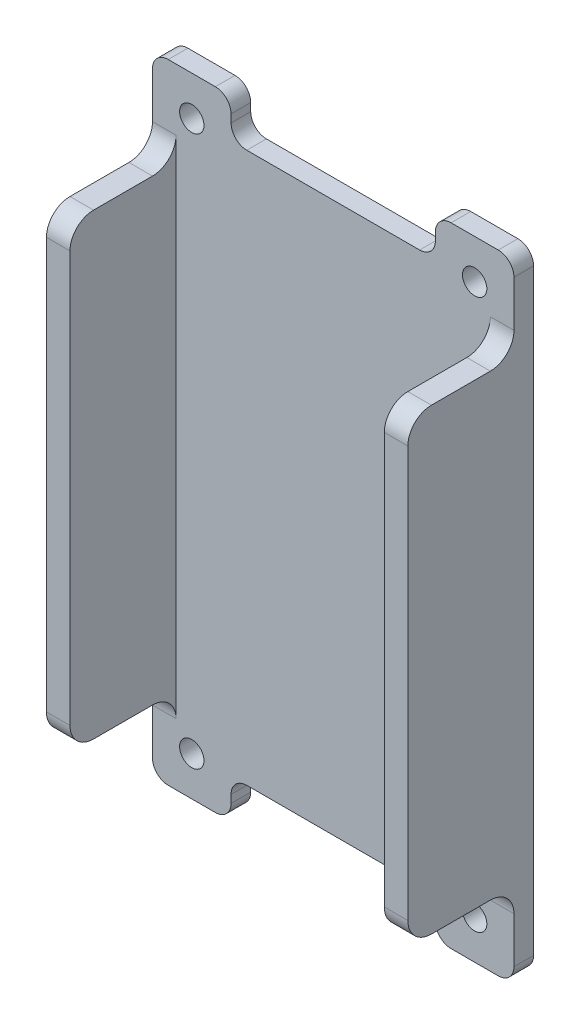
SolidWorks part; units mm, degrees
material "ABS"
ref_plane "Front Plane" through (0, 0, 0) normal (0, 0, 1) x (1, 0, 0)
ref_plane "Top Plane" through (0, 0, 0) normal (0, 1, 0) x (1, 0, 0)
ref_plane "Right Plane" through (0, 0, 0) normal (1, 0, 0) x (0, 0, -1)
sketch "Sketch1" plane through (0, 0, 0) normal (0, 0, 1) x (1, 0, 0)
  line L0 (0, -23.107) -> (0, 29972.0625) construction
  line L1 (-20, -19.15) -> (20, -19.15)
  line L2 (-20, -19.15) -> (-20, 39.15)
  line L3 (-20, 39.15) -> (20, 39.15)
  line L4 (20, -19.15) -> (20, 39.15)
  line L5 (-20, -19.15) -> (20, 39.15) construction
  line L6 (-20, 39.15) -> (20, -19.15) construction
  line L7 (4.4373, 10) -> (29962.6069, 10) construction
  line L8 (-13, 50) -> (-13, 45)
  line L10 (-23, -30) -> (-23, 50)
  line L11 (-23, 50) -> (-13, 50)
  line L12 (23, -30) -> (23, 50)
  line L13 (13, -30) -> (23, -30)
  line L14 (13, -25) -> (13, -30)
  line L15 (-13, 45) -> (13, 45)
  line L16 (13, 45) -> (13, 50)
  line L17 (13, 50) -> (23, 50)
  line L18 (-13, -25) -> (13, -25)
  line L19 (-13, -30) -> (-13, -25)
  line L20 (-23, -30) -> (-13, -30)
  line L21 (-23, 39.15) -> (-20, 39.15)
  line L22 (20, 39.15) -> (23, 39.15)
  line L23 (20, -19.15) -> (23, -19.15)
  line L24 (-20, -19.15) -> (-23, -19.15)
  circle A0 centre (-18, 45) radius 1.55
  circle A1 centre (18, 45) radius 1.55
  circle A2 centre (18, -25) radius 1.55
  circle A3 centre (-18, -25) radius 1.55
  point P0 (0, 10)
  point P10 (0, 10)
  point P26 (23, 10)
  point P33 (-23, 10)
  dimension "D3" = 3.1
  dimension "D1" = 40
  dimension "D2" = 58.3
  dimension "D4" = 3
  dimension "D5" = 5
  dimension "D6" = 5
  dimension "D7" = 5
  dimension "D8" = 5
  dimension "D9" = 35
  dimension "D10" = 5
  dimension "D11" = 2
  dimension "D12" = 10
extrude "Boss-Extrude2" add sketch "Sketch1" along normal blind 2.5 contours L1 L4 L3 L2 | L3 L22 L12 L17 L16 L15 L8 L11 L10 L21 A1 A0 | L4 L23 L12 L22 | L1 L24 L10 L20 L19 L18 L14 L13 L12 L23 A2 A3 | L24 L2 L21 L10 region at (0, 10, 0) region at (-21.5, 10, 0) region at (0, -23.4827, 0) region at (21.5, 10, 0) region at (0, 43.4827, 0)
extrude "Boss-Extrude3" add sketch "Sketch1<4>" along normal blind 16 contours L24 L2 L21 L10 | L4 L23 L12 L22 region at (-21.5, 10, 0) region at (21.5, 10, 0)
sketch "Sketch1<4>" plane through (0, 0, 0) normal (0, 0, 1) x (1, 0, 0) same geometry as "Sketch1"
fillet "Fillet1" radius 2 12 edges at (-23, -30, 1.25) (-13, -30, 1.25) (-13, -25, 1.25) (13, -25, 1.25) (13, -30, 1.25) (23, -30, 1.25) (13, 50, 1.25) (13, 45, 1.25) (-13, 45, 1.25) (-13, 50, 1.25) (-23, 50, 1.25) (23, 50, 1.25)
fillet "Fillet2" radius 3 8 edges at (-21.5, -19.15, 2.5) (-21.5, -19.15, 16) (-21.5, 39.15, 16) (-21.5, 39.15, 2.5) (21.5, -19.15, 16) (21.5, -19.15, 2.5) (21.5, 39.15, 16) (21.5, 39.15, 2.5)
ref_plane "Plane1" through (0, 10, 0) normal (0, -1, 0) x (-1, 0, 0)
